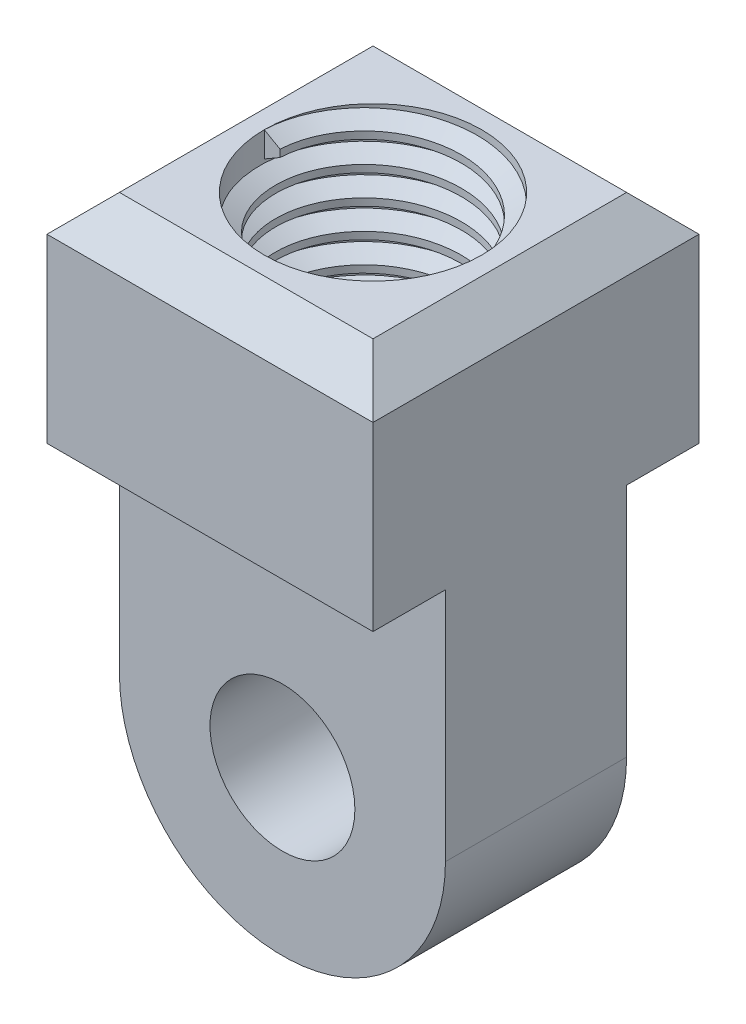
SolidWorks part; units mm, degrees
ref_plane "Front Plane" through (0, 0, 0) normal (0, 0, 1) x (1, 0, 0)
ref_plane "Top Plane" through (0, 0, 0) normal (0, 1, 0) x (1, 0, 0)
ref_plane "Right Plane" through (0, 0, 0) normal (1, 0, 0) x (0, 0, -1)
sketch "Sketch1" plane through (0, 0, 0) normal (0, 0, 1) x (1, 0, 0)
  line L0 (9, 0) -> (9, 6.5)
  line L1 (9, 6.5) -> (0, 6.5)
  line L2 (0, 6.5) -> (0, 0)
  arc A0 (0, 0) -> (9, 0) centre (4.5, 0) ccw
  circle A1 centre (4.5, 0) radius 2
  point P7 (4.5, -4.5)
  dimension "D1" = 4.5
  dimension "D2" = 4
  dimension "D3" = 11
extrude "Boss-Extrude1" add sketch "Sketch1" along normal blind 5
sketch "Sketch2" plane through (0, 6.5, 0) normal (0, 1, 0) x (1, 0, 0)
  line L0 (9, 0) -> (0, 0) construction
  line L1 (0, 2) -> (9, 2)
  line L2 (0, 2) -> (0, -7)
  line L3 (0, -7) -> (9, -7)
  line L4 (9, 2) -> (9, -7)
  line L5 (9, -5) -> (0, -5) construction
  line L6 (0, -5) -> (0, 0) construction
  line L7 (9, -5) -> (9, 0) construction
  dimension "D1" = 2
  dimension "D2" = 2
extrude "Boss-Extrude2" add sketch "Sketch2" along normal blind 6
chamfer "Chamfer1" distance 1 angle 45 4 edges at (4.5, 12.5, -2) (9, 12.5, 2.5) (0, 12.5, 2.5) (4.5, 12.5, 7)
sketch "Sketch3" plane through (0, 12.5, 0) normal (0, 1, 0) x (1, 0, 0)
  circle A0 centre (4.5, -2.5) radius 3
  dimension "D1" = 6
extrude "Cut-Extrude1" cut sketch "Sketch3" against normal blind 5
thread "Thread1" pitch 0.8 method extrude profile "Thread Profile1" start angle 0, offset 0, length 5, pitch 0.8, diameter 6
ref_plane "Plane1" through (1.5, 12.5, 2.5) normal (0, 0, 1) x (-1, 0, 0)
sketch "Thread Profile1" plane through (1.5, 12.5, 2.5) normal (0, 0, 1) x (-1, 0, 0)
  line L0 (0, 0) -> (0, 0.8) construction
  line L11 (0, 0) -> (0, 0.7)
  line L12 (0, 0.7) -> (-0.433, 0.45)
  line L13 (-0.433, 0.45) -> (-0.433, 0.25)
  line L15 (-0.433, 0.25) -> (0, 0)
  line L17 (-0.433, 0.35) -> (0, 0.35) construction
  point P2 (0, 0)
  dimension "Pitch" = 0.8
  dimension "Profile_Angle" = 60
  dimension "Profile_Land" = 0.2
  dimension "Profile_Height" = 0.433
